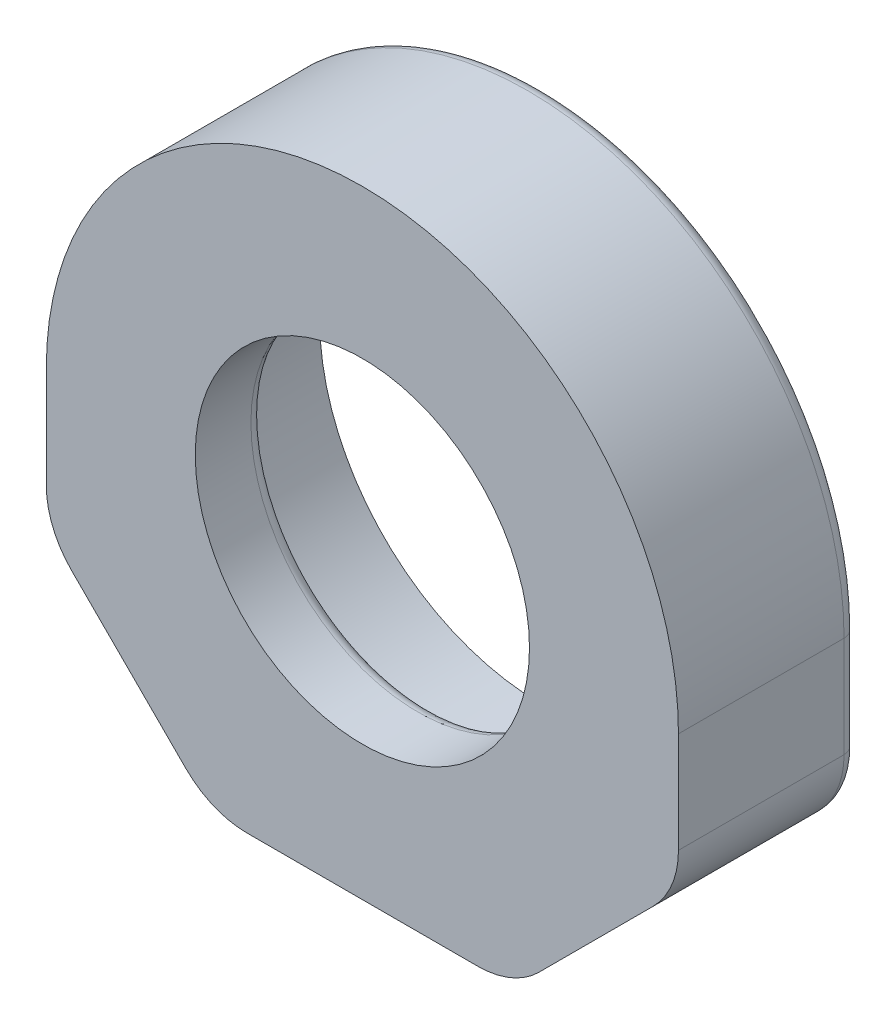
SolidWorks part; units mm, degrees
ref_plane "Front Plane" through (0, 0, 0) normal (0, 0, 1) x (1, 0, 0)
ref_plane "Top Plane" through (0, 0, 0) normal (0, 1, 0) x (1, 0, 0)
ref_plane "Right Plane" through (0, 0, 0) normal (1, 0, 0) x (0, 0, -1)
sketch "Sketch1" plane through (0, 0, 0) normal (0, 0, 1) x (1, 0, 0)
  line L1 (-36.5125, 0) -> (-36.5125, -34.8451)
  line L2 (-36.5125, -34.8451) -> (36.5125, -34.8451)
  line L3 (36.5125, 0) -> (36.5125, -34.8451)
  arc A0 (36.5125, 0) -> (-36.5125, 0) centre (0, 0) ccw
extrude "Boss-Extrude1" add sketch "Sketch1" along normal blind 63.5 and the other way blind 63.5 contours A0 L1 L2 L3
sketch "Sketch3" plane through (0, 0, 0) normal (0, 1, 0) x (1, 0, 0)
  circle A0 centre (0, 0) radius 36.5125
extrude "Boss-Extrude2" add sketch "Sketch3" along normal blind 101.6
sketch "Sketch4" plane through (0, 0, -63.5) normal (0, 0, -1) x (-1, 0, 0)
  circle A0 centre (0, 0) radius 19.304
extrude "Cut-Extrude1" cut sketch "Sketch4" against normal through all
sketch "Sketch5" plane through (0, 0, -63.5) normal (0, 0, -1) x (-1, 0, 0)
  circle A0 centre (0, 0) radius 25.654
extrude "Cut-Extrude2" cut sketch "Sketch5" against normal blind 12.7
sketch "Sketch6" plane through (0, 0, 63.5) normal (0, 0, 1) x (1, 0, 0)
  circle A0 centre (0, 0) radius 25.654
extrude "Cut-Extrude3" cut sketch "Sketch6" against normal blind 12.7
sketch "Sketch7" plane through (0, 101.6, 0) normal (0, 1, 0) x (1, 0, 0)
  circle A0 centre (0, 0) radius 30.4165
extrude "Cut-Extrude4" cut sketch "Sketch7" against normal blind 78.834
chamfer "Chamfer1" distance 19.05 angle 45 2 edges at (36.5125, -34.8451, 0) (-36.5125, -34.8451, 0)
fillet "Fillet1" radius 10 4 edges at (36.5125, -15.7951, 0) (17.4625, -34.8451, 0) (-17.4625, -34.8451, 0) (-36.5125, -15.7951, 0)
fillet "Fillet2" radius 1.5875 24 edges at (36.5125, -5.8265, -63.5) (35.7513, -15.4798, -63.5) (26.9875, -25.3201, -63.5) (17.1472, -34.0839, -63.5) (0, -34.8451, -63.5) (-17.1472, -34.0839, -63.5) (-26.9875, -25.3201, -63.5) (-35.7513, -15.4798, -63.5) (-36.5125, -5.8265, -63.5) (36.5125, -5.8265, 63.5) (35.7513, -15.4798, 63.5) (26.9875, -25.3201, 63.5) (17.1472, -34.0839, 63.5) (0, -34.8451, 63.5) (-17.1472, -34.0839, 63.5) (-26.9875, -25.3201, 63.5) (-35.7513, -15.4798, 63.5) (-36.5125, -5.8265, 63.5) (-19.304, 0, -50.8) (19.304, 0, 50.8) (0, 101.6, 30.4165) (0, 101.6, 36.5125) (0, 36.5125, -63.5) (0, 36.5125, 63.5)
sketch "Sketch8" plane through (0, 0, 0) normal (1, 0, 0) x (0, 0, -1)
  line L0 (61.9125, -34.8451) -> (-61.9125, -34.8451) construction
  line L1 (42.7834, -34.8451) -> (-78.3082, -34.8451)
  line L2 (42.7834, -34.8451) -> (42.7834, 106.0495)
  line L3 (42.7834, 106.0495) -> (-78.3082, 106.0495)
  line L4 (-78.3082, -34.8451) -> (-78.3082, 106.0495)
extrude "Cut-Extrude5" cut sketch "Sketch8" against normal through all both and the other way through all
